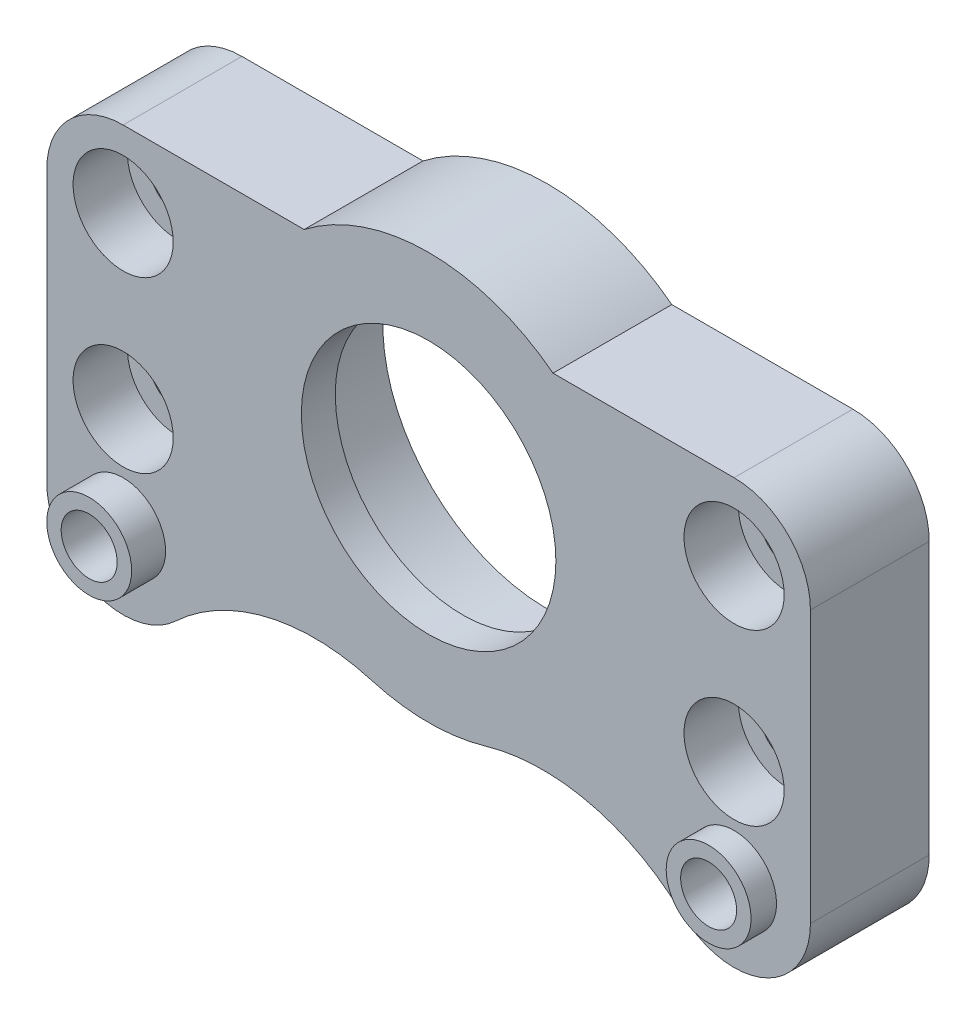
SolidWorks part; units mm, degrees
ref_plane "Front Plane" through (0, 0, 0) normal (0, 0, 1) x (1, 0, 0)
ref_plane "Top Plane" through (0, 0, 0) normal (0, 1, 0) x (1, 0, 0)
ref_plane "Right Plane" through (0, 0, 0) normal (1, 0, 0) x (0, 0, -1)
sketch "Sketch1" plane through (0, 0, 0) normal (0, 0, 1) x (1, 0, 0)
  circle A0 centre (0, 0) radius 9.5 construction
  circle A1 centre (0, 0) radius 2.5 construction
  dimension "D1" = 19
  dimension "D2" = 5
sketch "Sketch2" plane through (0, 0, 0) normal (0, 0, 1) x (1, 0, 0)
  line L0 (0, 0) -> (0, 12) construction
  line L1 (-7.3314, 9.5) -> (-18, 9.5)
  line L2 (-22.5, 0) -> (0, 0) construction
  line L3 (-22.5, 5) -> (-22.5, -11)
  line L5 (22.5, 5) -> (22.5, -11)
  line L6 (7.3314, 9.5) -> (18, 9.5)
  arc A0 (7.3314, 9.5) -> (-7.3314, 9.5) centre (0, 0) ccw
  circle A2 centre (0, 0) radius 9.5 construction
  arc A3 (-18, 9.5) -> (-22.5, 5) centre (-18, 5) ccw
  circle A4 centre (-18, 5) radius 1.65
  arc A5 (-22.5, -11) -> (-14.9232, -14.2838) centre (-18, -11) ccw
  circle A6 centre (-18, -11) radius 1.65
  circle A7 centre (-18, -5) radius 1.65
  arc A8 (-3.3592, -11.5202) -> (3.3592, -11.5202) centre (0, 0) ccw
  circle A12 centre (18, -5) radius 1.65
  circle A13 centre (18, -11) radius 1.65
  arc A14 (22.5, -11) -> (14.9232, -14.2838) centre (18, -11) cw
  circle A15 centre (18, 5) radius 1.65
  arc A16 (18, 9.5) -> (22.5, 5) centre (18, 5) cw
  arc A17 (-14.9232, -14.2838) -> (-3.3592, -11.5202) centre (-6.7183, -23.0405) cw
  arc A18 (14.9232, -14.2838) -> (3.3592, -11.5202) centre (6.7183, -23.0405) ccw
  point P22 (0, 0)
  dimension "D1" = 2.5
  dimension "D2" = 4.5
  dimension "D3" = 3.3
  dimension "D4" = 4.5
  dimension "D7" = 2.5
  dimension "D8" = 12
  dimension "D5" = 10
  dimension "D6" = 6
  dimension "D9" = 45
extrude "Boss-Extrude1" add sketch "Sketch2" along normal blind 7
sketch "Sketch3" plane through (0, 0, 0) normal (0, 0, 1) x (1, 0, 0)
  circle A2 centre (0, 0) radius 9.7
  circle A3 centre (0, 0) radius 9.7
  dimension "D1" = 0.2
extrude "Cut-Extrude1" cut sketch "Sketch3" along normal blind 5
sketch "Sketch4" plane through (0, 0, 5) normal (0, 0, -1) x (-1, 0, 0)
  circle A0 centre (0, 0) radius 7.5
  dimension "D1" = 15
extrude "Cut-Extrude2" cut sketch "Sketch4" against normal blind 5
sketch "Sketch6" plane through (0, 0, 0) normal (0, 0, -1) x (-1, 0, 0)
  line L0 (0, 0) -> (0, 12) construction
  line L1 (-16.3257, -8.1) -> (-19.6743, -8.1)
  line L2 (-19.6743, -8.1) -> (-21.3486, -11)
  line L3 (-21.3486, -11) -> (-19.6743, -13.9)
  line L4 (-19.6743, -13.9) -> (-16.3257, -13.9)
  line L5 (-16.3257, -13.9) -> (-14.6514, -11)
  line L6 (-14.6514, -11) -> (-16.3257, -8.1)
  line L7 (14.6514, -11) -> (16.3257, -8.1)
  line L8 (16.3257, -13.9) -> (14.6514, -11)
  line L9 (19.6743, -13.9) -> (16.3257, -13.9)
  line L10 (21.3486, -11) -> (19.6743, -13.9)
  line L11 (19.6743, -8.1) -> (21.3486, -11)
  line L12 (16.3257, -8.1) -> (19.6743, -8.1)
  circle A0 centre (-18, -11) radius 2.9 construction
  arc A1 (7.3314, 9.5) -> (-7.3314, 9.5) centre (0, 0) ccw construction
  circle A2 centre (18, -11) radius 2.9 construction
  dimension "D1" = 5.8
extrude "Cut-Extrude3" cut sketch "Sketch6" against normal blind 2.5
sketch "Sketch8" plane through (0, 0, 7) normal (0, 0, 1) x (1, 0, 0)
  circle A0 centre (18, -5) radius 2.95
  circle A1 centre (18, 5) radius 2.95
  circle A2 centre (-18, 5) radius 2.95
  circle A3 centre (-18, -5) radius 2.95
  dimension "D1" = 5.9
extrude "Cut-Extrude4" cut sketch "Sketch8" against normal blind 3.2
sketch "Sketch9" plane through (0, 0, 7) normal (0, 0, 1) x (1, 0, 0)
  line L0 (0, 0) -> (0, 7.5) construction
  circle A0 centre (-18, -11) radius 1.65
  circle A1 centre (-18, -11) radius 2.5
  circle A3 centre (-18, -11) radius 1.65 construction
  circle A4 centre (0, 0) radius 7.5 construction
  circle A5 centre (18, -11) radius 2.5
  circle A6 centre (18, -11) radius 1.65
  dimension "D1" = 5
extrude "Boss-Extrude2" add sketch "Sketch9" along normal blind 1.5
other "Move Face1" face at (-15.5, -11, 8.5) offset 0.5 parameters "D1"=0.5
